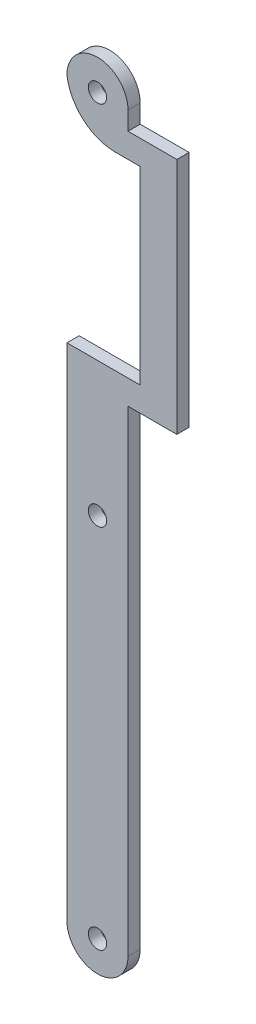
SolidWorks part; units mm, degrees
ref_plane "前视基准面" through (0, 0, 0) normal (0, 0, 1) x (1, 0, 0)
ref_plane "上视基准面" through (0, 0, 0) normal (0, 1, 0) x (1, 0, 0)
ref_plane "右视基准面" through (0, 0, 0) normal (1, 0, 0) x (0, 0, -1)
sketch "草图1" plane through (0, 0, 0) normal (0, 0, 1) x (1, 0, 0)
  line L0 (0, 60) -> (0, -60) construction
  line L1 (5, 60) -> (5, -60)
  line L2 (-5, 60) -> (-5, -60)
  line L3 (55, 0) -> (-55, 0) construction
  arc A0 (5, 60) -> (-5, 60) centre (0, 60) ccw
  arc A1 (-5, -60) -> (5, -60) centre (0, -60) ccw
  circle A2 centre (0, 60) radius 1.5
  circle A3 centre (0, -60) radius 1.5
  circle A5 centre (0, 0) radius 1.5
  point P3 (0, 0)
  dimension "D3" = 3
  dimension "D4" = 60
  dimension "D5" = 3
  dimension "D1" = 60
  dimension "D2" = 10
extrude "凸台-拉伸1" add sketch "草图1" along normal blind 2
sketch "草图2" plane through (-5, 0, 0) normal (-1, 0, 0) x (0, 0, 1)
  line L0 (0, 60) -> (0, -60) construction
  line L1 (0, 57) -> (2, 57)
  line L2 (0, 57) -> (0, 53)
  line L3 (0, 53) -> (2, 53)
  line L4 (2, 57) -> (2, 53)
  line L5 (2, 60) -> (2, -60) construction
  line L6 (2, 65) -> (0, 65) construction
  dimension "D1" = 8
  dimension "D2" = 4
extrude "凸台-拉伸5" add sketch "草图2" against normal blind 18
sketch "草图5" plane through (0, 53, 0) normal (0, -1, 0) x (1, 0, 0)
  line L0 (13, 2) -> (5, 2) construction
  line L1 (13, 0) -> (10, 0)
  line L2 (13, 0) -> (13, 2)
  line L3 (13, 2) -> (10, 2)
  line L4 (10, 0) -> (10, 2)
  dimension "D1" = 3
extrude "凸台-拉伸6" add sketch "草图5" along normal blind 35
sketch "草图7" plane through (13, 0, 0) normal (1, 0, 0) x (0, 0, -1)
  line L0 (0, 57) -> (0, 18) construction
  line L1 (-2, 18) -> (0, 18)
  line L2 (-2, 18) -> (-2, 22)
  line L3 (-2, 22) -> (0, 22)
  line L4 (0, 18) -> (0, 22)
  dimension "D1" = 4
extrude "凸台-拉伸9" add sketch "草图7" against normal up to surface (8 mm away) up to face at (5, -3.5, 1)
sketch "草图9" plane through (0, 0, 0) normal (0, 0, -1) x (-1, 0, 0)
  line L0 (5, 60) -> (5, -60) construction
  line L1 (-5, 53) -> (5, 53)
  line L2 (-5, 53) -> (-5, 22)
  line L3 (-5, 22) -> (5, 22)
  line L4 (5, 53) -> (5, 22)
  dimension "D1" = 31
extrude "切除-拉伸2" cut sketch "草图9" against normal blind 15
sketch "草图10" plane through (0, 0, 0) normal (0, 0, -1) x (-1, 0, 0)
  line L0 (5, 22) -> (-10, 22) construction
  line L1 (-10, 53) -> (-7, 53)
  line L2 (-10, 53) -> (-10, 22)
  line L3 (-10, 22) -> (-7, 22)
  line L4 (-7, 53) -> (-7, 22)
  dimension "D1" = 3
extrude "凸台-拉伸10" add sketch "草图10" against normal up to surface (2 mm away) up to face at (3.8333, 25, 2)
fillet "圆角1" radius 8 1 edges at (-5, 53, 1)
